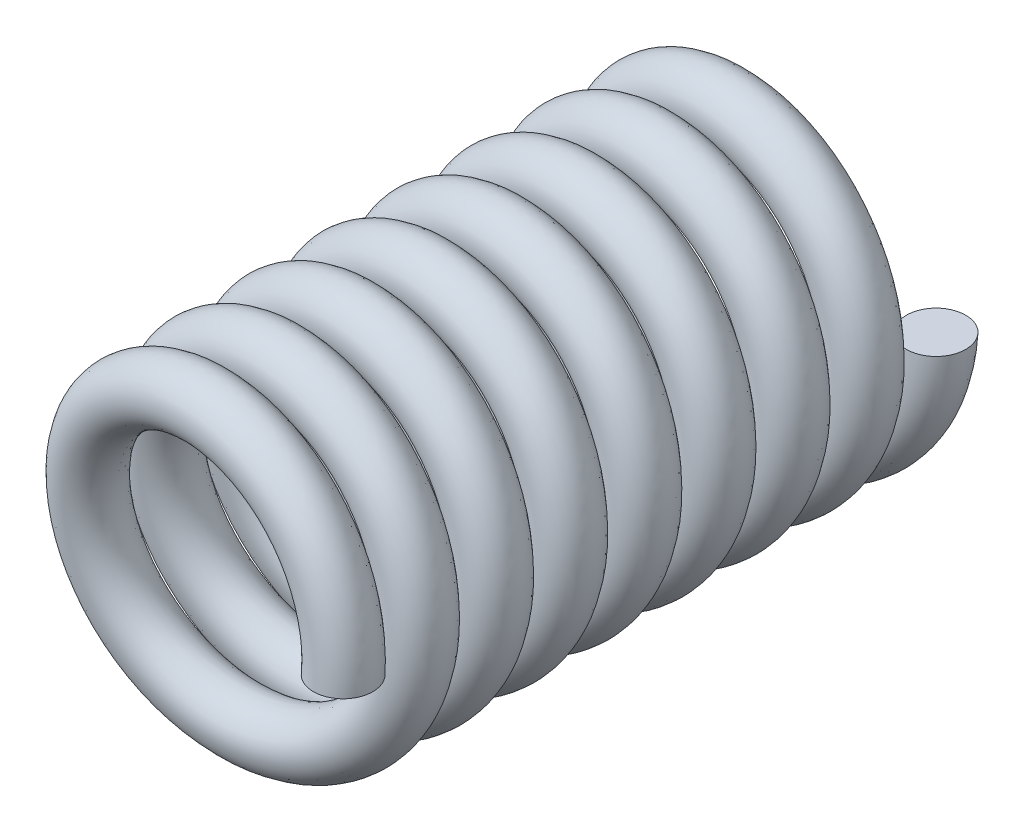
SolidWorks part; units mm, degrees
material "Copper"
ref_plane "Front Plane" through (0, 0, 0) normal (0, 0, 1) x (1, 0, 0)
ref_plane "Top Plane" through (0, 0, 0) normal (0, 1, 0) x (1, 0, 0)
ref_plane "Right Plane" through (0, 0, 0) normal (1, 0, 0) x (0, 0, -1)
sketch "Sketch1" plane through (0, 0, 0) normal (0, 0, 1) x (1, 0, 0)
  circle A0 centre (0, 0) radius 25.4
curve "Helix/Spiral1" pitch 12.7 height 101.6 turns 8
sketch "Sketch2" plane through (0, 0, 0) normal (0, 1, 0) x (1, 0, 0)
  circle A0 centre (25.0141, -101.6) radius 5.08
  spline S0 degree 3 poles (25.0141, 0) (25.4279, -0.1896) (25.5909, -0.5711) (23.8044, -1.1415) (20.1332, -1.7124) (14.8669, -2.2831) (8.423, -2.8539) (1.3118, -3.4247) (-5.9033, -3.9955) (-12.6507, -4.5663) (-18.3961, -5.1371) (-22.6841, -5.7079) (-25.1753, -6.2787) (-25.6721, -6.8494) (-24.1353, -7.4202) (-20.6866, -7.991) (-15.5992, -8.5618) (-9.2761, -9.1326) (-2.2182, -9.7034) (5.0154, -10.2742) (11.8517, -10.8449) (17.7492, -11.4157) (22.2407, -11.9865) (24.9704, -12.5573) (25.722, -13.1281) (24.436, -13.6989) (21.2143, -14.2697) (16.3121, -14.8404) (10.1177, -15.4112) (3.1219, -15.982) (-4.1213, -16.5528) (-11.038, -17.1236) (-17.0803, -17.6944) (-21.7696, -18.2652) (-24.7344, -18.836) (-25.7398, -19.4067) (-24.7062, -19.9775) (-21.7155, -20.5483) (-17.0046, -21.1191) (-10.9467, -21.6899) (-4.0216, -22.2607) (3.2221, -22.8315) (10.2105, -23.4022) (16.3901, -23.973) (21.2713, -24.5438) (24.4675, -25.1146) (25.7255, -25.6854) (24.9457, -26.2562) (22.1897, -26.827) (17.676, -27.3978) (11.762, -27.9685) (4.9163, -28.5393) (-2.3188, -29.1101) (-9.3702, -29.6809) (-15.6794, -30.2517) (-20.7466, -30.8225) (-24.1702, -31.3933) (-25.6792, -31.964) (-25.154, -32.5348) (-22.6362, -33.1056) (-18.3253, -33.6764) (-12.5627, -34.2472) (-5.805, -34.818) (1.4126, -35.3888) (8.5183, -35.9596) (14.9493, -36.5303) (20.1959, -37.1011) (23.8428, -37.6719) (25.6009, -38.2427) (25.3311, -38.8135) (23.0546, -39.3843) (18.9518, -39.9551) (13.3477, -40.5258) (6.6863, -41.0966) (-0.5047, -41.6674) (-7.6558, -42.2382) (-14.2005, -42.809) (-19.6202, -43.3798) (-23.4857, -43.9506) (-25.4907, -44.5213) (-25.4765, -45.0921) (-23.4442, -45.6629) (-19.5547, -46.2337) (-14.1161, -46.8045) (-7.5594, -47.3753) (-0.4038, -47.9461) (6.7838, -48.5169) (13.434, -49.0876) (19.02, -49.6584) (23.0993, -50.2292) (25.3488, -50.8) (25.5903, -51.3708) (23.8046, -51.9416) (20.1332, -52.5124) (14.867, -53.0831) (8.423, -53.6539) (1.3118, -54.2247) (-5.9033, -54.7955) (-12.6507, -55.3663) (-18.3961, -55.9371) (-22.6841, -56.5079) (-25.1753, -57.0787) (-25.6721, -57.6494) (-24.1353, -58.2202) (-20.6866, -58.791) (-15.5992, -59.3618) (-9.2761, -59.9326) (-2.2182, -60.5034) (5.0154, -61.0742) (11.8517, -61.6449) (17.7492, -62.2157) (22.2407, -62.7865) (24.9704, -63.3573) (25.722, -63.9281) (24.436, -64.4989) (21.2143, -65.0697) (16.3121, -65.6404) (10.1177, -66.2112) (3.1219, -66.782) (-4.1213, -67.3528) (-11.038, -67.9236) (-17.0803, -68.4944) (-21.7696, -69.0652) (-24.7344, -69.636) (-25.7398, -70.2067) (-24.7062, -70.7775) (-21.7155, -71.3483) (-17.0046, -71.9191) (-10.9467, -72.4899) (-4.0216, -73.0607) (3.2221, -73.6315) (10.2105, -74.2022) (16.3901, -74.773) (21.2713, -75.3438) (24.4675, -75.9146) (25.7255, -76.4854) (24.9457, -77.0562) (22.1897, -77.627) (17.676, -78.1978) (11.762, -78.7685) (4.9163, -79.3393) (-2.3188, -79.9101) (-9.3702, -80.4809) (-15.6794, -81.0517) (-20.7466, -81.6225) (-24.1702, -82.1933) (-25.6792, -82.764) (-25.154, -83.3348) (-22.6362, -83.9056) (-18.3253, -84.4764) (-12.5627, -85.0472) (-5.805, -85.618) (1.4126, -86.1888) (8.5183, -86.7596) (14.9493, -87.3303) (20.1959, -87.9011) (23.8428, -88.4719) (25.6009, -89.0427) (25.3311, -89.6135) (23.0546, -90.1843) (18.9518, -90.7551) (13.3477, -91.3258) (6.6863, -91.8966) (-0.5047, -92.4674) (-7.6558, -93.0382) (-14.2005, -93.609) (-19.6202, -94.1798) (-23.4857, -94.7506) (-25.4907, -95.3213) (-25.4765, -95.8921) (-23.4442, -96.4629) (-19.5547, -97.0337) (-14.1161, -97.6045) (-7.5594, -98.1753) (-0.4038, -98.7461) (6.7838, -99.3169) (13.4339, -99.8876) (19.0201, -100.4585) (23.0987, -101.0289) (24.6003, -101.4104) (25.0141, -101.6) knots 0 0 0 0 0.005618 0.011236 0.016854 0.022472 0.02809 0.033708 0.039326 0.044944 0.050562 0.05618 0.061798 0.067416 0.073034 0.078652 0.08427 0.089888 0.095506 0.101124 0.106742 0.11236 0.117978 0.123596 0.129213 0.134831 0.140449 0.146067 0.151685 0.157303 0.162921 0.168539 0.174157 0.179775 0.185393 0.191011 0.196629 0.202247 0.207865 0.213483 0.219101 0.224719 0.230337 0.235955 0.241573 0.247191 0.252809 0.258427 0.264045 0.269663 0.275281 0.280899 0.286517 0.292135 0.297753 0.303371 0.308989 0.314607 0.320225 0.325843 0.331461 0.337079 0.342697 0.348315 0.353933 0.359551 0.365169 0.370787 0.376404 0.382022 0.38764 0.393258 0.398876 0.404494 0.410112 0.41573 0.421348 0.426966 0.432584 0.438202 0.44382 0.449438 0.455056 0.460674 0.466292 0.47191 0.477528 0.483146 0.488764 0.494382 0.5 0.505618 0.511236 0.516854 0.522472 0.52809 0.533708 0.539326 0.544944 0.550562 0.55618 0.561798 0.567416 0.573034 0.578652 0.58427 0.589888 0.595506 0.601124 0.606742 0.61236 0.617978 0.623596 0.629213 0.634831 0.640449 0.646067 0.651685 0.657303 0.662921 0.668539 0.674157 0.679775 0.685393 0.691011 0.696629 0.702247 0.707865 0.713483 0.719101 0.724719 0.730337 0.735955 0.741573 0.747191 0.752809 0.758427 0.764045 0.769663 0.775281 0.780899 0.786517 0.792135 0.797753 0.803371 0.808989 0.814607 0.820225 0.825843 0.831461 0.837079 0.842697 0.848315 0.853933 0.859551 0.865169 0.870787 0.876404 0.882022 0.88764 0.893258 0.898876 0.904494 0.910112 0.91573 0.921348 0.926966 0.932584 0.938202 0.94382 0.949438 0.955056 0.960674 0.966292 0.97191 0.977528 0.983146 0.988764 0.994382 1 1 1 1 construction
sweep "Sweep1" add profiles "Sketch2" path "Helix/Spiral1"
